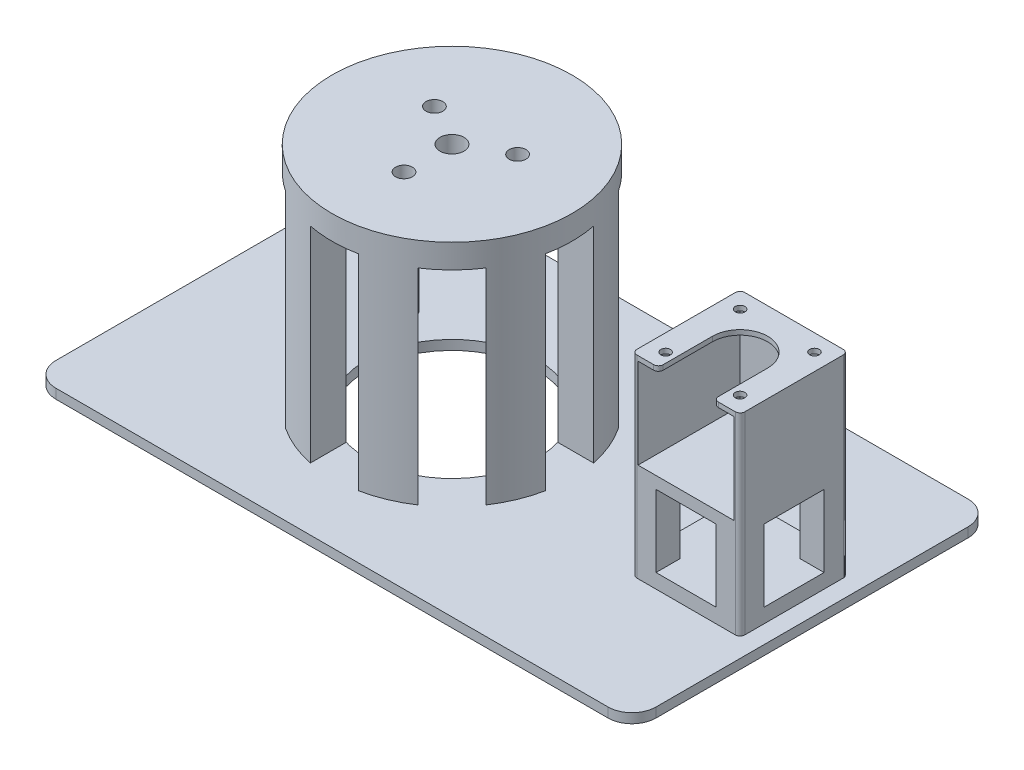
SolidWorks part; units mm, degrees
ref_plane "Front" through (0, 0, 0) normal (0, 0, 1) x (1, 0, 0)
ref_plane "Top" through (0, 0, 0) normal (0, 1, 0) x (1, 0, 0)
ref_plane "Right" through (0, 0, 0) normal (1, 0, 0) x (0, 0, -1)
sketch "Sketch1" plane through (0, 0, 0) normal (0, 1, 0) x (1, 0, 0)
  circle A0 centre (0, 0) radius 50
  dimension "D1" = 100
extrude "Boss-Extrude1" add sketch "Sketch1" along normal blind 99.5
sketch "Sketch2" plane through (0, 0, 0) normal (0, 1, 0) x (1, 0, 0)
  line L1 (-90, 75) -> (140, 75)
  line L2 (-100, 65) -> (-100, -65)
  line L3 (-90, -75) -> (140, -75)
  line L4 (150, 65) -> (150, -65)
  arc A1 (-100, -65) -> (-90, -75) centre (-90, -65) ccw
  arc A2 (140, -75) -> (150, -65) centre (140, -65) ccw
  arc A3 (140, 75) -> (150, 65) centre (140, 65) cw
  arc A4 (-90, 75) -> (-100, 65) centre (-90, 65) ccw
  point P7 (-100, 0)
  dimension "D1" = 150
  dimension "D4" = 10
  dimension "D2" = 150
  dimension "D3" = 100
extrude "Boss-Extrude2" add sketch "Sketch2" along normal blind 4 contours L2 A1 L3 A2 L4 A3 L1 A4
sketch "Sketch3" plane through (0, 99.5, 0) normal (0, 1, 0) x (1, 0, 0)
  circle A0 centre (0, 0) radius 5
  dimension "D1" = 10
extrude "Cut-Extrude1" cut sketch "Sketch3" against normal blind 20
sketch "Sketch4" plane through (0, 4, 0) normal (0, 1, 0) x (1, 0, 0)
  line L1 (97.5, 22.5) -> (142.5, 22.5)
  line L2 (97.5, 22.5) -> (97.5, -22.5)
  line L3 (97.5, -22.5) -> (142.5, -22.5)
  line L4 (142.5, 22.5) -> (142.5, -22.5)
  line L5 (97.5, 22.5) -> (142.5, -22.5) construction
  line L6 (97.5, -22.5) -> (142.5, 22.5) construction
  point P0 (120, 0)
  dimension "D1" = 45
  dimension "D2" = 120
sketch "Sketch5" plane through (0, 99.5, 0) normal (0, 1, 0) x (1, 0, 0)
  circle A0 centre (0, 0) radius 35.5
  dimension "D1" = 71
sketch "Sketch6" plane through (0, 0, 0) normal (0, -1, 0) x (1, 0, 0)
  circle A3 centre (0, 0) radius 35.5
  circle A4 centre (0, 0) radius 35.5
  dimension "D1" = 0
extrude "Cut-Extrude2" cut sketch "Sketch6" against normal offset from surface (89.5 mm away) 10 up to face at (0, 99.5, 5)
sketch "Sketch7" plane through (0, 0, 0) normal (0, 0, 1) x (1, 0, 0)
  line L0 (-90, 4) -> (140, 4) construction
  line L1 (-10, 4) -> (10, 4)
  line L2 (-10, 4) -> (-10, 89.5)
  line L3 (-10, 89.5) -> (10, 89.5)
  line L4 (10, 4) -> (10, 89.5)
  line L6 (35.5, 99.5) -> (-35.5, 99.5) construction
  point P8 (0, 89.5)
  dimension "D1" = 20
  dimension "D2" = 10
extrude "Cut-Extrude3" cut sketch "Sketch7" against normal through all both and the other way through all
pattern_circular "CirPattern1" count 8 over 360 about axis through (0, 99.5, 0) along (0, -1, 0) of "Cut-Extrude3"
sketch "Sketch8" plane through (0, 89.5, 0) normal (0, -1, 0) x (1, 0, 0)
  circle A0 centre (0, 20) radius 1.5
  circle A1 centre (17.3205, -10) radius 1.5
  circle A2 centre (-17.3205, -10) radius 1.5
  point P9 (0, 0)
  dimension "D1" = 3
  dimension "D2" = 20
  dimension "D3" = 3
extrude "Extrude-Thin1" add sketch "Sketch8" along normal blind 40 thin thin type one direction wall 3
extrude "Cut-Extrude4" cut sketch "Sketch8<2>" against normal through all
sketch "Sketch8<2>" plane through (0, 89.5, 0) normal (0, -1, 0) x (1, 0, 0) same geometry as "Sketch8"
sketch "Sketch9" plane through (0, 99.5, 0) normal (0, 1, 0) x (1, 0, 0)
  circle A0 centre (0, -20) radius 3.5
  circle A1 centre (-17.3205, 10) radius 1.5
  circle A2 centre (-17.3205, 10) radius 1.5
  circle A3 centre (17.3205, 10) radius 1.5
  circle A4 centre (17.3205, 10) radius 1.5
  circle A5 centre (0, -20) radius 1.5
  circle A6 centre (0, -20) radius 1.5
  circle A7 centre (-17.3205, 10) radius 3.5
  circle A8 centre (17.3205, 10) radius 3.5
  dimension "D1" = 0
  dimension "D2" = 0
  dimension "D3" = 0
  dimension "D4" = 2
extrude "Cut-Extrude5" cut sketch "Sketch9" against normal blind 5
fillet "Fillet1" radius 2 3 edges at (17.3205, 89.5, -5.5) (-17.3205, 89.5, -5.5) (0, 89.5, 24.5)
extrude "Boss-Extrude3" add sketch "Sketch4" along normal blind 41
sketch "Sketch10" plane through (0, 45, 0) normal (0, 1, 0) x (1, 0, 0)
  line L0 (97.5, -22.5) -> (97.5, 22.5)
  line L1 (97.5, 22.5) -> (142.5, 22.5)
  line L2 (142.5, 22.5) -> (142.5, -22.5)
extrude "Extrude-Thin2" add sketch "Sketch10" along normal blind 37.5 thin thin type one direction wall 2.5
sketch "Sketch11" plane through (0, 82.5, 0) normal (0, 1, 0) x (1, 0, 0)
  line L1 (108.5, 0) -> (108.5, -22.5)
  line L2 (131.5, 0) -> (131.5, -22.5)
  line L4 (104.5, 15.5) -> (135.5, 15.5) construction
  line L5 (104.5, 15.5) -> (104.5, -15.5) construction
  line L6 (104.5, -15.5) -> (135.5, -15.5) construction
  line L7 (135.5, 15.5) -> (135.5, -15.5) construction
  line L8 (140, 20) -> (140, -22.5)
  line L9 (140, -22.5) -> (142.5, -22.5)
  line L10 (142.5, -22.5) -> (142.5, 22.5)
  line L11 (142.5, 22.5) -> (97.5, 22.5)
  line L12 (97.5, 22.5) -> (97.5, -22.5)
  line L13 (97.5, -22.5) -> (100, -22.5)
  line L14 (100, -22.5) -> (100, 20)
  line L15 (100, 20) -> (140, 20)
  line L18 (142.5, -22.5) -> (142.5, 22.5)
  line L19 (142.5, 22.5) -> (97.5, 22.5)
  line L20 (97.5, 22.5) -> (97.5, -22.5)
  line L21 (97.5, -22.5) -> (142.5, -22.5)
  line L24 (104.5, 15.5) -> (135.5, -15.5) construction
  line L25 (104.5, -15.5) -> (135.5, 15.5) construction
  circle A0 centre (120, 0) radius 11.5
  circle A1 centre (104.5, 15.5) radius 2
  circle A2 centre (135.5, 15.5) radius 2
  circle A3 centre (135.5, -15.5) radius 2
  circle A4 centre (104.5, -15.5) radius 2
  point P12 (120, 22.5)
  line M20 (140, 20) -> (140, -22.5)
  line M21 (140, -22.5) -> (142.5, -22.5)
  line M22 (142.5, -22.5) -> (142.5, 22.5)
  line M23 (142.5, 22.5) -> (97.5, 22.5)
  line M24 (97.5, 22.5) -> (97.5, -22.5)
  line M25 (97.5, -22.5) -> (100, -22.5)
  line M26 (100, -22.5) -> (100, 20)
  line M27 (100, 20) -> (140, 20)
  dimension "D2" = 23
  dimension "D3" = 4
  dimension "D4" = 31
  dimension "D1" = 0
extrude "Boss-Extrude4" add sketch "Sketch11" along normal blind 2 contours M27 M20 M21 M22 M23 M24 M25 M26 | A0 L2 L21 L1 A4 A3 A2 A1 M20 M27 M26 region at (107.9164, 82.5, 11.25) region at (98.75, 82.5, 21.8636)
fillet "Fillet2" radius 2 6 edges at (108.5, 83.5, 22.5) (97.5, 44.25, -22.5) (142.5, 44.25, -22.5) (131.5, 83.5, 22.5) (97.5, 44.25, 22.5) (142.5, 44.25, 22.5)
sketch "Sketch12" plane through (0, 0, 22.5) normal (0, 0, 1) x (1, 0, 0)
  line L0 (100, 45) -> (140, 45) construction
  line L1 (107.5, 40) -> (132.5, 40)
  line L2 (107.5, 40) -> (107.5, 10)
  line L3 (107.5, 10) -> (132.5, 10)
  line L4 (132.5, 40) -> (132.5, 10)
  line L5 (107.5, 40) -> (132.5, 10) construction
  line L6 (107.5, 10) -> (132.5, 40) construction
  line L7 (142.5, 84.5) -> (142.5, 4) construction
  line L8 (99.5, 4) -> (140.5, 4) construction
  point P0 (120, 25)
  point P5 (120, 40)
  point P12 (120, 45)
  dimension "D1" = 5
  dimension "D2" = 10
  dimension "D3" = 6
extrude "Cut-Extrude6" cut sketch "Sketch12" against normal through all
sketch "Sketch13" plane through (142.5, 0, 0) normal (1, 0, 0) x (0, 0, -1)
  line L0 (-22.5, 10) -> (-22.5, 40) construction
  line L1 (-12.5, 10) -> (12.5, 10)
  line L2 (-12.5, 10) -> (-12.5, 40)
  line L3 (-12.5, 40) -> (12.5, 40)
  line L4 (12.5, 10) -> (12.5, 40)
  line L5 (-12.5, 10) -> (12.5, 40) construction
  line L6 (-12.5, 40) -> (12.5, 10) construction
  line L7 (22.5, 40) -> (-22.5, 40) construction
  line L8 (22.5, 10) -> (-22.5, 10) construction
  line L9 (-22.5, 4) -> (-22.5, 84.5) construction
  line L10 (-20.5, 84.5) -> (20.5, 84.5) construction
  point P0 (0, 25)
  point P13 (0, 40)
  point P16 (0, 84.5)
  dimension "D1" = 10
extrude "Cut-Extrude7" cut sketch "Sketch13" against normal up to surface (45 mm away) up to face at (97.5, 44.25, 0)
split "Split1" bodies to split 117 resulting bodies 118 119 120 split by face at (25, 4, 0)
